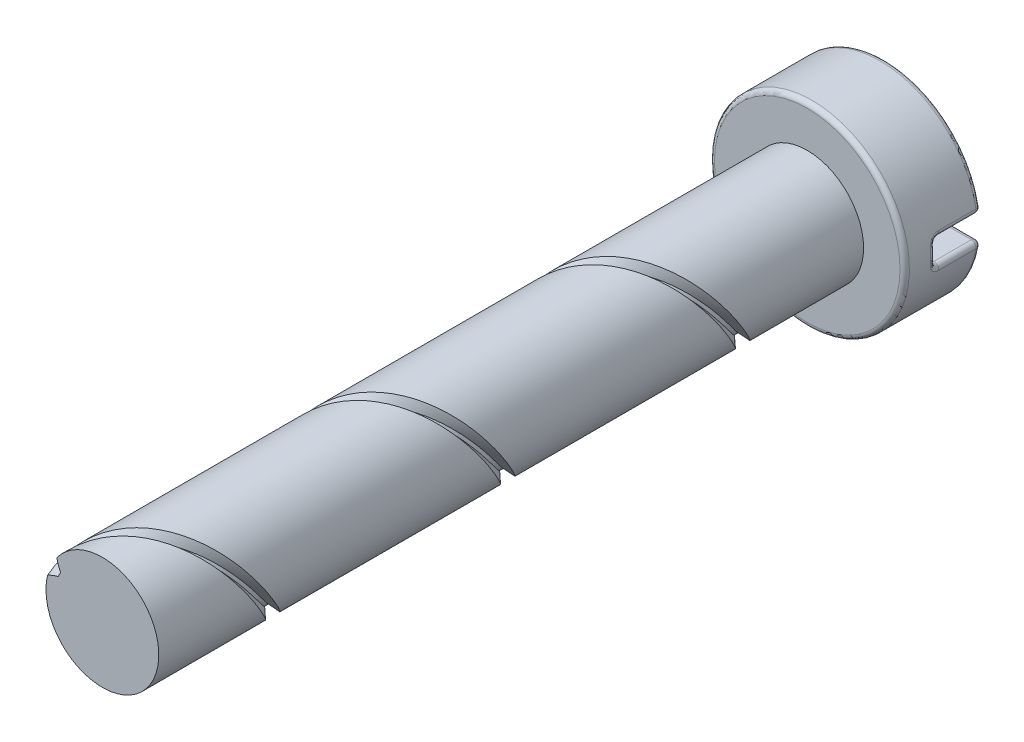
SolidWorks part; units mm, degrees
ref_plane "Front Plane" through (0, 0, 0) normal (0, 0, 1) x (1, 0, 0)
ref_plane "Top Plane" through (0, 0, 0) normal (0, 1, 0) x (1, 0, 0)
ref_plane "Right Plane" through (0, 0, 0) normal (1, 0, 0) x (0, 0, -1)
sketch "Sketch1" plane through (0, 0, 0) normal (0, 0, 1) x (1, 0, 0)
  circle A0 centre (0, 0) radius 2.4
  dimension "D1" = 4.8
extrude "Boss-Extrude1" add sketch "Sketch1" along normal blind 30
sketch "Sketch2" plane through (0, 0, 0) normal (0, 0, -1) x (-1, 0, 0)
  circle A0 centre (0, 0) radius 4.15
  dimension "D1" = 8.3
extrude "Boss-Extrude2" add sketch "Sketch2" along normal blind 3.3
thread "Thread1" pitch 0.7 start angle 0, offset 1, length 29, pitch 10, diameter 4.8
ref_plane "Plane1" through (-2.4, 0, 31) normal (0, -1, 0) x (-1, 0, 0)
sketch "Thread Profile1" plane through (-2.4, 0, 31) normal (0, -1, 0) x (-1, 0, 0)
  line L0 (0, 0) -> (0, 0.7) construction
  line L11 (0, 0) -> (0, 0.6125)
  line L12 (0, 0.6125) -> (-0.3789, 0.3937)
  line L13 (-0.3789, 0.3937) -> (-0.3789, 0.2187)
  line L15 (-0.3789, 0.2187) -> (0, 0)
  line L17 (-0.3789, 0.3062) -> (0, 0.3062) construction
  point P2 (0, 0)
  dimension "Pitch" = 0.7
  dimension "Profile_Angle" = 60
  dimension "Profile_Land" = 0.175
  dimension "Profile_Height" = 0.3789
sketch "Sketch4" plane through (0, 0, -3.3) normal (0, 0, -1) x (-1, 0, 0)
  line L1 (5, 0.5) -> (-5, 0.5)
  line L2 (5, 0.5) -> (5, -0.5)
  line L3 (5, -0.5) -> (-5, -0.5)
  line L4 (-5, 0.5) -> (-5, -0.5)
  line L5 (5, 0.5) -> (-5, -0.5) construction
  line L6 (5, -0.5) -> (-5, 0.5) construction
  point P0 (0, 0)
  dimension "D1" = 1
  dimension "D2" = 10
extrude "Cut-Extrude1" cut sketch "Sketch4" against normal blind 2
fillet "Fillet1" radius 0.2 13 edges at (0, -0.5, -1.3) (0, 0.5, -1.3) (-4.15, 0, 0) (-4.1198, 0.5, -2.3) (4.1198, 0.5, -2.3) (-4.15, 0, -1.3) (4.15, 0, -1.3) (-4.1198, -0.5, -2.3) (4.1198, -0.5, -2.3) (0, -4.15, -3.3) (0, -0.5, -3.3) (0, 4.15, -3.3) (0, 0.5, -3.3)
